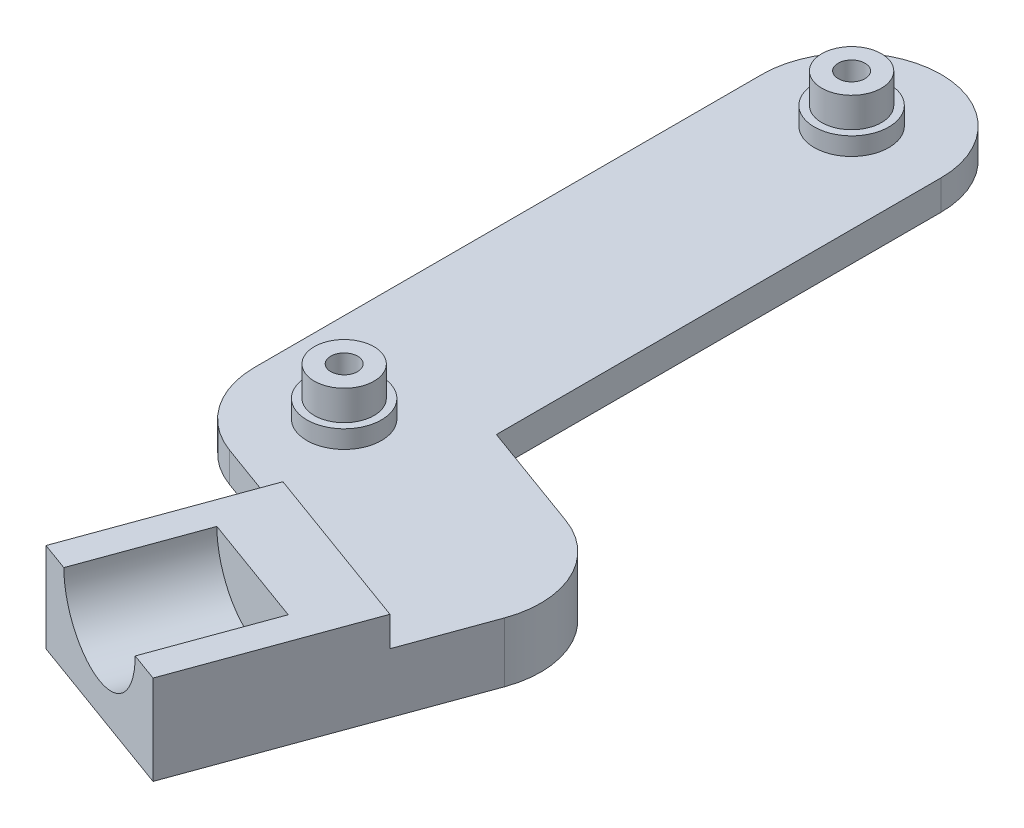
SolidWorks part; units mm, degrees
ref_plane "정면" through (0, 0, 0) normal (0, 0, 1) x (1, 0, 0)
ref_plane "윗면" through (0, 0, 0) normal (0, 1, 0) x (1, 0, 0)
ref_plane "우측면" through (0, 0, 0) normal (1, 0, 0) x (0, 0, -1)
sketch "스케치1" plane through (0, 0, 0) normal (0, 1, 0) x (1, 0, 0)
  line L0 (0, 0) -> (0, 85) construction
  line L1 (-15, 0) -> (-15, 85)
  line L2 (15, 0) -> (15, 85)
  arc A0 (-15, 0) -> (15, 0) centre (0, 0) ccw
  arc A1 (15, 85) -> (-15, 85) centre (0, 85) ccw
  point P3 (0, 42.5)
  dimension "D2" = 15
  dimension "D1" = 85
extrude "보스-돌출1" add sketch "스케치1" along normal blind 5 contours A1 L1 A0 L2
sketch "스케치2" plane through (0, 5, 0) normal (0, 1, 0) x (1, 0, 0)
  line L0 (0, 85) -> (0, 0) construction
  circle A0 centre (0, 85) radius 6.25
  circle A1 centre (0, 0) radius 6.25
  point P9 (0, 18.3018)
  dimension "D2" = 12.5
  dimension "D3" = 12.5
  dimension "D1" = 85
extrude "보스-돌출2" add sketch "스케치2" along normal blind 3
sketch "스케치3" plane through (0, 8, 0) normal (0, 1, 0) x (1, 0, 0)
  circle A0 centre (0, 85) radius 5
  circle A1 centre (0, 0) radius 5
  dimension "D1" = 10
  dimension "D2" = 10
extrude "보스-돌출3" add sketch "스케치3" along normal blind 5
sketch "스케치4" plane through (0, 0, 0) normal (0, -1, 0) x (1, 0, 0)
  line L0 (0, -85) -> (0, -20) construction
  dimension "D1" = 65
hole_wizard "M4 남비 머리 나사용 카운터보어1" positions "스케치5" profile "스케치7" counterbore size "M4" standard "ISO" end condition through all
sketch "스케치5" plane through (0, 0, 0) normal (0, -1, 0) x (-1, 0, 0)
  point P3 (0, 85)
  point P10 (0, 0)
  dimension "D1" = 85
sketch "스케치7" plane through (0, 0, -85) normal (1, 0, 0) x (0, 0, -1)
  line L0 (0, 0) -> (0, 13)
  line L1 (0, 13) -> (2.25, 13)
  line L3 (2.25, 13) -> (2.25, 4)
  line L4 (2.25, 4) -> (4.5, 4)
  line L5 (4.5, 4) -> (4.5, 0)
  line L7 (4.5, 0) -> (0, 0)
  line L11 (0, -6.35) -> (0, 107.95) construction
  dimension "관통 구멍 지름" = 4.5
  dimension "관통 구멍 깊이" = 13
  dimension "카운터보어 지름" = 9
  dimension "카운터보어 깊이" = 4
sketch "스케치8" plane through (0, 0, 0) normal (0, -1, 0) x (1, 0, 0)
  line L0 (0, 0) -> (28.1908, 10.2606) construction
  line L1 (15, 0) -> (15, -85) construction
  line L2 (0, 0) -> (28.1908, 10.2606) construction
  line L3 (-5.1303, 14.0954) -> (23.0605, 24.356)
  line L4 (15, -10.5031) -> (33.3211, -3.8348)
  line L5 (15, 0) -> (15, -10.5031)
  arc A1 (33.3211, -3.8348) -> (23.0605, 24.356) centre (28.1908, 10.2606) ccw
  arc A2 (15, 0) -> (-15, 0) centre (0, 0) ccw construction
  arc A3 (15, 0) -> (-5.1303, 14.0954) centre (0, 0) ccw
  point P3 (15, 5.4596)
  point P8 (0, 0)
  dimension "D3" = 15
  dimension "D1" = 110
  dimension "D2" = 30
extrude "보스-돌출4" add sketch "스케치8" against normal blind 5
sketch "스케치9" plane through (0, 0, 0) normal (0, -1, 0) x (1, 0, 0)
  line L0 (28.1908, 10.2606) -> (17.9302, 38.4514) construction
  line L1 (23.0605, 24.356) -> (-5.1303, 14.0954) construction
  line L2 (28.1908, 10.2606) -> (17.9302, 38.4514) construction
  line L3 (14.0954, 5.1303) -> (3.8348, 33.3211)
  line L4 (42.2862, 15.3909) -> (32.0256, 43.5817)
  line L5 (3.8348, 33.3211) -> (-1.6248, 48.3211)
  line L6 (32.0256, 43.5817) -> (26.566, 58.5817)
  line L7 (-1.6248, 48.3211) -> (26.566, 58.5817)
  arc A0 (14.0954, 5.1303) -> (42.2862, 15.3909) centre (28.1908, 10.2606) ccw
  point P5 (23.0605, 24.356)
  dimension "D3" = 15
  dimension "D5" = 30
  dimension "D1" = 30
  dimension "D2" = 90
  dimension "D4" = 15
  dimension "D6" = 30
extrude "보스-돌출5" add sketch "스케치9" against normal blind 5 and the other way blind 5
sketch "스케치13" plane through (0, 5, 0) normal (0, 1, 0) x (1, 0, 0)
  line L0 (42.2862, -15.3909) -> (26.566, -58.5817) construction
  line L1 (-1.6248, -48.3211) -> (8.9651, -19.2257) construction
  line L2 (26.566, -58.5817) -> (-1.6248, -48.3211) construction
  line L3 (37.1559, -29.4863) -> (26.566, -58.5817)
  line L4 (-1.6248, -48.3211) -> (8.9651, -19.2257)
  line L5 (26.566, -58.5817) -> (-1.6248, -48.3211)
  line L6 (8.9651, -19.2257) -> (37.1559, -29.4863)
extrude "보스-돌출6" add sketch "스케치13" along normal blind 5
sketch "스케치15" plane through (-15.7202, 0, 43.1908) normal (-0.342, 0, 0.9397) x (0.9397, 0, 0.342)
  line L0 (15, 10) -> (45, 10) construction
  circle A0 centre (30, 10) radius 10
  dimension "D1" = 20
extrude "컷-돌출2" cut sketch "스케치15" against normal blind 20
